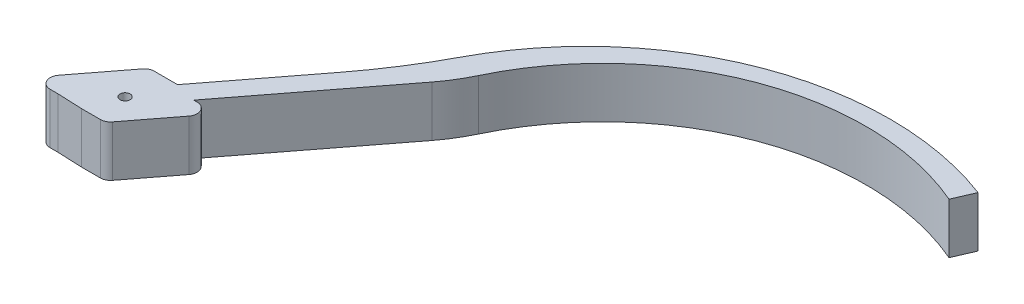
SolidWorks part; units mm, degrees
ref_plane "Front Plane" through (0, 0, 0) normal (0, 0, 1) x (1, 0, 0)
ref_plane "Top Plane" through (0, 0, 0) normal (0, 1, 0) x (1, 0, 0)
ref_plane "Right Plane" through (0, 0, 0) normal (1, 0, 0) x (0, 0, -1)
sketch "Sketch1" plane through (0, 0, 0) normal (0, 1, 0) x (1, 0, 0)
  line L4 (47.7948, 18.9954) -> (48.8939, 21.5354)
  line L5 (0, 0) -> (-12.9802, -16.9114)
  line L7 (-19.4955, -25.4) -> (-16.395, -25.5322)
  line L8 (4.122, 1.1987) -> (-10.2896, -17.5776)
  line L9 (-19.4955, -25.4) -> (-23.0335, -25.4)
  line L11 (-23.0335, -25.4) -> (-16.5182, -16.9114)
  line L12 (-12.9802, -16.9114) -> (-16.5182, -16.9114)
  line L13 (-16.395, -25.5322) -> (-13.4, -25.5322)
  line L15 (-13.4, -25.5322) -> (-7.2946, -17.5776)
  line L16 (-10.2896, -17.5776) -> (-7.2946, -17.5776)
  arc A1 (4.122, 1.1987) -> (47.7948, 18.9954) centre (34.6814, -11.309) cw
  arc A2 (0, 0) -> (48.8939, 21.5354) centre (35.3973, -14.0939) cw
  circle A3 centre (-14.9451, -21.5234) radius 0.635
  point P17 (-10.3626, -17.6728)
  point P18 (-12.9802, -16.9114)
  point P19 (-14.9451, -21.5234)
  dimension "D1" = 33.02
  dimension "D5" = 38.1
  dimension "D6" = 1.27
  dimension "D2" = 2.54
  dimension "D3" = 2.54
  dimension "D4" = 25.4
extrude "Boss-Extrude2" add sketch "Sketch1" along normal blind 6.35
fillet "Fillet3" radius 20.32 1 edges at (4.122, 3.175, -1.1987)
fillet "Fillet4" radius 66.04 1 edges at (0, 3.175, 0)
fillet "Fillet5" radius 1.27 4 edges at (-16.5182, 3.175, 16.9114) (-23.0335, 3.175, 25.4) (-7.2946, 3.175, 17.5776) (-13.4, 3.175, 25.5322)
